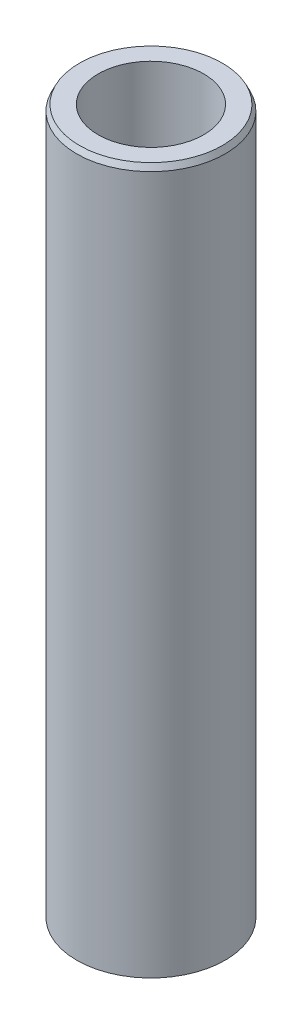
SolidWorks part; units mm, degrees
ref_plane "Front Plane" through (0, 0, 0) normal (0, 0, 1) x (1, 0, 0)
ref_plane "Top Plane" through (0, 0, 0) normal (0, 1, 0) x (1, 0, 0)
ref_plane "Right Plane" through (0, 0, 0) normal (1, 0, 0) x (0, 0, -1)
sketch "Sketch1" plane through (0, 0, 0) normal (0, 1, 0) x (1, 0, 0)
  circle A0 centre (0, 0) radius 50
  dimension "SHAFT_OD" = 100
extrude "Boss-Extrude1" add sketch "Sketch1" along normal blind 476.0606
sketch "Sketch2" plane through (0, 0, 0) normal (0, 1, 0) x (1, 0, 0)
  circle A0 centre (0, 0) radius 35.5496
  dimension "BORE_D" = 71.0992
extrude "Cut-Extrude1" cut sketch "Sketch2" along normal through all
chamfer "Chamfer1" distance 3.9251 angle 25.8 2 edges at (0, 476.0606, 50) (0, 0, 50) first distance on face at (0, 476.0606, 50) first distance on face at (0, 0, 35.5496)
